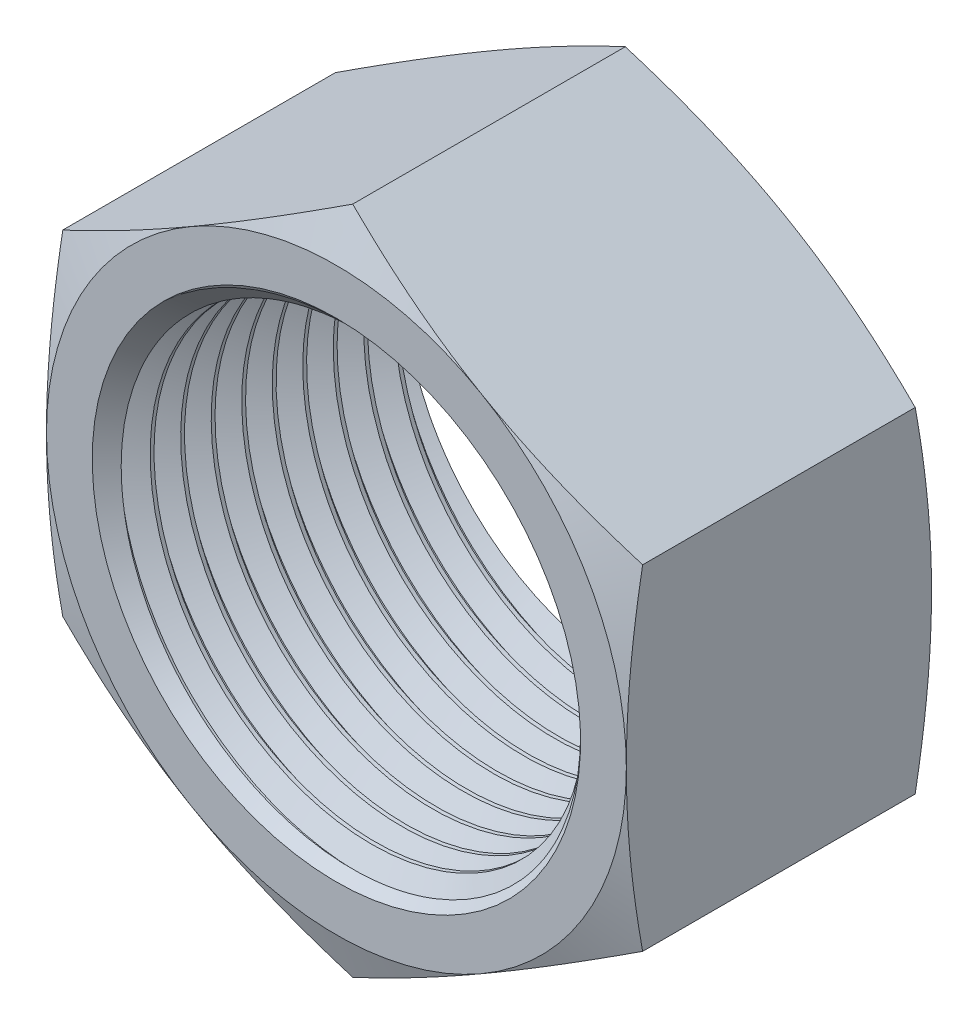
SolidWorks part; units mm, degrees
ref_plane "Front Plane" through (0, 0, 0) normal (0, 0, 1) x (1, 0, 0)
ref_plane "Top Plane" through (0, 0, 0) normal (0, 1, 0) x (1, 0, 0)
ref_plane "Right Plane" through (0, 0, 0) normal (1, 0, 0) x (0, 0, -1)
sketch "Sketch1" plane through (0, 0, 0) normal (0, 0, 1) x (1, 0, 0)
  line L1 (9.5, -5.4848) -> (9.5, 5.4848)
  line L2 (9.5, 5.4848) -> (0, 10.9697)
  line L3 (0, 10.9697) -> (-9.5, 5.4848)
  line L4 (-9.5, 5.4848) -> (-9.5, -5.4848)
  line L5 (-9.5, -5.4848) -> (0, -10.9697)
  line L6 (0, -10.9697) -> (9.5, -5.4848)
  circle A0 centre (0, 0) radius 9.5 construction
  circle A1 centre (0, 0) radius 8
  point P10 (0, -8)
  point P11 (0, 0)
  point P12 (0, 0)
  dimension "ID" = 16
  dimension "Hex Width" = 19
extrude "Boss-Extrude1" add sketch "Sketch1" along normal mid plane 10
sketch "Sketch2" plane through (0, 0, 5) normal (0, 0, 1) x (1, 0, 0)
  circle A0 centre (0, 0) radius 8 construction
  circle A1 centre (0, 0) radius 8
sketch "Sketch5" plane through (0, 0, 5) normal (0, 0, 1) x (1, 0, 0)
  circle A0 centre (0, 0) radius 9.5 construction
  circle A1 centre (0, 0) radius 9.5
extrude "Cut-Extrude2" cut sketch "Sketch5" against normal through all draft 70 flip side to cut
sketch "Sketch12" plane through (0, 0, 0) normal (1, 0, 0) x (0, 0, -1)
  line L0 (5, -10.9697) -> (-5, -10.9697) construction
  line L1 (-4.4651, -10.9697) -> (5, -10.9697) construction
  dimension "D1" = 10
mirror "Mirror1" about plane through (0, 0, 0) normal (0, 0, 1) of "Cut-Extrude2"
curve "Helix/Spiral1" pitch 1 height 11 radius 8 centre (0, 0, 5) axis (0, 0, -1) start towards (0, 1, 0) parameters "Pitch"=1
sketch "Sketch3" plane through (0, 0, 0) normal (1, 0, 0) x (0, 0, -1)
  line L0 (-5, 8) -> (-5.875, 8)
  line L1 (-5.875, 8) -> (-5.5, 7.3505)
  line L2 (-5.5, 7.3505) -> (-5.375, 7.3505)
  line L3 (-5.375, 7.3505) -> (-5, 8)
  line L4 (-5.4375, 7.3505) -> (-5.4375, 8) construction
  line L5 (-5.6875, 7.6752) -> (-5.1875, 7.6752) construction
  dimension "D1" = 60
  dimension "D2" = 0.125
  dimension "D3" = 0.5
sweep "Sweep1" add profiles "Sketch3" path "Helix/Spiral1"
sketch "Sketch4" plane through (0, 0, 5) normal (0, 0, 1) x (1, 0, 0)
  circle A0 centre (0, 0) radius 8 construction
  circle A1 centre (0, 0) radius 8
extrude "Cut-Extrude1" cut sketch "Sketch4" along normal through all draft 20 and the other way through all draft 45 draft outward yes
sketch "Sketch11" plane through (0, 0, -5) normal (0, 0, -1) x (-1, 0, 0)
  circle A0 centre (0, 0) radius 9.5 construction
  circle A1 centre (0, 0) radius 9.5
extrude "Cut-Extrude6" cut sketch "Sketch11" along normal through all
fillet "Fillet1" [suppressed] radius 0.1
fillet "Fillet2" [suppressed] radius 0.1
equation "\"D2@Sketch3\" = \"Pitch@Helix/Spiral1\"*.125"
equation "\"D3@Sketch3\" = \"Pitch@Helix/Spiral1\"*.50"
equation "\"D3@Helix/Spiral1\" = \"Thickness@Boss-Extrude1\" + \"Pitch@Helix/Spiral1\""
equation "\"D1@Sketch12\"=\"Thickness@Boss-Extrude1\""
